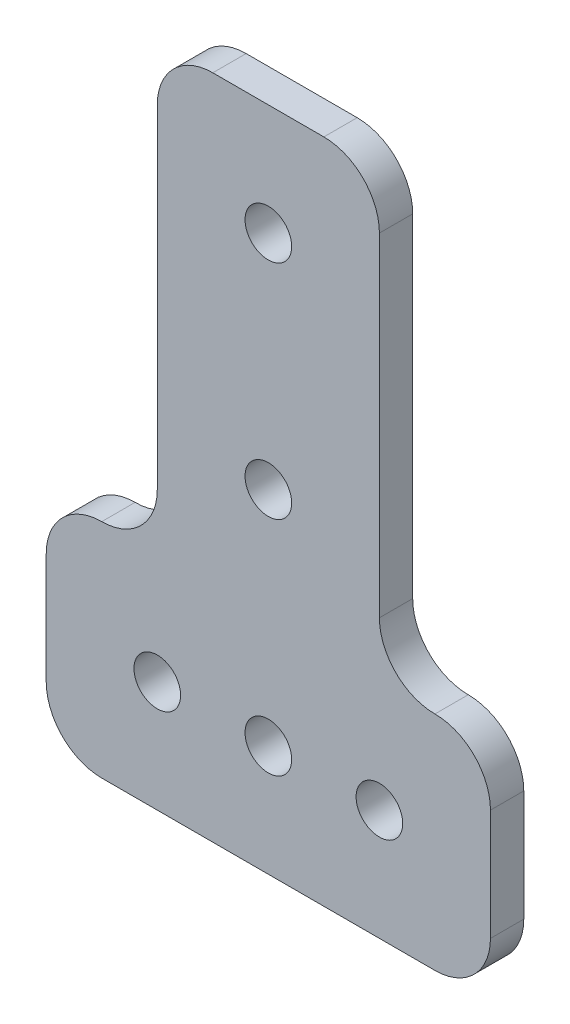
SolidWorks part; units mm, degrees
material "Thornel Mat VMA"
ref_plane "前视基准面" through (0, 0, 0) normal (0, 0, 1) x (1, 0, 0)
ref_plane "上视基准面" through (0, 0, 0) normal (0, 1, 0) x (1, 0, 0)
ref_plane "右视基准面" through (0, 0, 0) normal (1, 0, 0) x (0, 0, -1)
sketch "草图1" plane through (0, 0, 0) normal (0, 0, 1) x (1, 0, 0)
  line L0 (10, 0) -> (10, 40)
  line L1 (0, 0) -> (10, 0)
  line L2 (0, 0) -> (0, -20)
  line L3 (0, -20) -> (40, -20)
  line L4 (40, 0) -> (40, -20)
  line L5 (10, 40) -> (30, 40)
  line L6 (30, 40) -> (30, 0)
  line L7 (30, 0) -> (40, 0)
  line L8 (20, 40) -> (20, -20) construction
  line L9 (0, -10) -> (40, -10) construction
  circle A0 centre (20, -10) radius 2.1
  circle A1 centre (10, -10) radius 2.1
  circle A2 centre (30, -10) radius 2.1
  circle A3 centre (20, 10) radius 2.1
  circle A4 centre (20, 30) radius 2.1
  dimension "D6" = 4.2
  dimension "D7" = 20
  dimension "D9" = 4.2
  dimension "D10" = 4.2
  dimension "D1" = 60
  dimension "D2" = 20
  dimension "D3" = 10
  dimension "D4" = 20
  dimension "D5" = 40
  dimension "D8" = 10
  dimension "D12" = 20
  dimension "D11" = 3
extrude "凸台-拉伸1" add sketch "草图1" along normal blind 3
fillet "圆角1" radius 5 7 edges at (10, 40, 1.5) (30, 40, 1.5) (40, -20, 1.5) (40, 0, 1.5) (30, 0, 1.5) (10, 0, 1.5) (0, 0, 1.5)
fillet "圆角2" radius 5 1 edges at (0, -20, 1.5)
